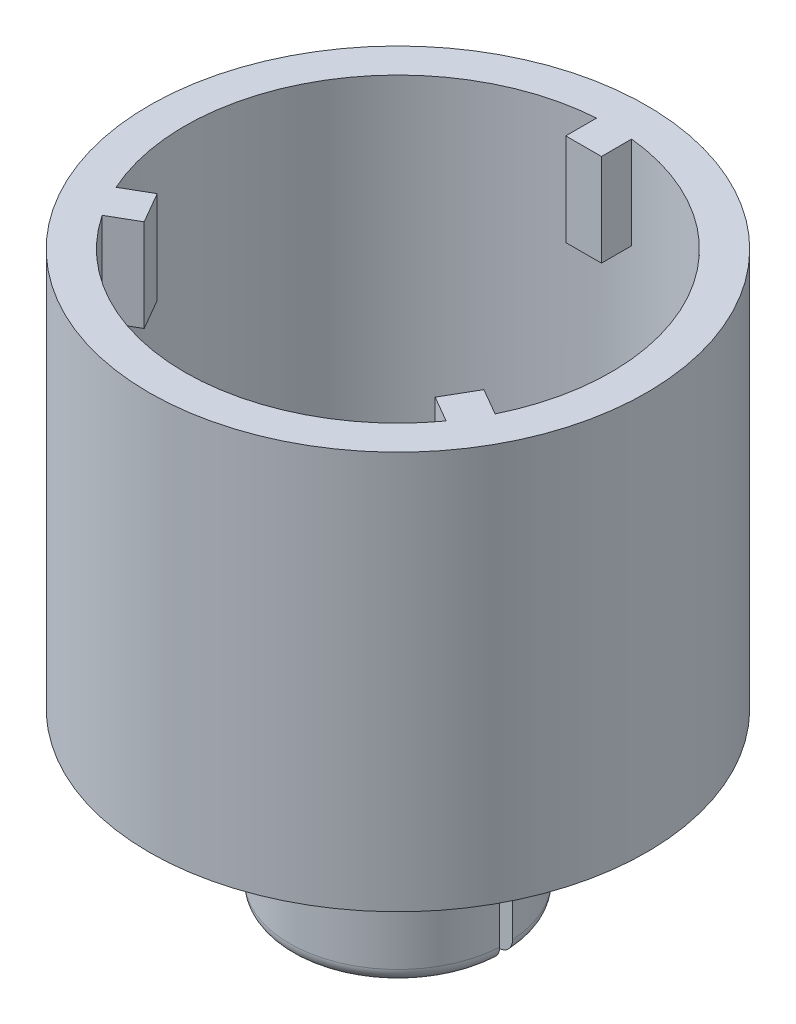
SolidWorks part; units mm, degrees
ref_plane "Front Plane" through (0, 0, 0) normal (0, 0, 1) x (1, 0, 0)
ref_plane "Top Plane" through (0, 0, 0) normal (0, 1, 0) x (1, 0, 0)
ref_plane "Right Plane" through (0, 0, 0) normal (1, 0, 0) x (0, 0, -1)
sketch "Sketch1" plane through (0, 0, 0) normal (0, 1, 0) x (1, 0, 0)
  circle A0 centre (0, 0) radius 35
  dimension "D1" = 70
extrude "Boss-Extrude1" add sketch "Sketch1" along normal blind 56
sketch "Sketch2" plane through (0, 56, 0) normal (0, 1, 0) x (1, 0, 0)
  circle A0 centre (0, 0) radius 30
  dimension "D1" = 60
extrude "Cut-Extrude1" cut sketch "Sketch2" against normal blind 46.9
sketch "Sketch3" plane through (0, 0, 0) normal (0, -1, 0) x (1, 0, 0)
  circle A0 centre (0, 0) radius 19.5
  dimension "D1" = 39
extrude "Boss-Extrude2" add sketch "Sketch3" along normal blind 7
sketch "Sketch4" plane through (0, -7, 0) normal (0, -1, 0) x (1, 0, 0)
  circle A0 centre (0, 0) radius 15.25
  dimension "D1" = 30.5
extrude "Boss-Extrude3" add sketch "Sketch4" along normal blind 16
fillet "Fillet1" radius 5 1 edges at (0, 0, -19.5)
sketch "Sketch5" plane through (0, 56, 0) normal (0, 1, 0) x (1, 0, 0)
  line L0 (-1.9905, 29.9339) -> (-1.9905, 25.6053)
  line L1 (-1.9905, 25.6053) -> (3.0302, 25.6053)
  line L2 (3.0302, 25.6053) -> (3.0302, 29.8466)
  line L3 (26.9188, -13.2431) -> (23.1701, -11.0788)
  line L4 (23.1701, -11.0788) -> (20.6597, -15.4269)
  line L5 (20.6597, -15.4269) -> (24.3328, -17.5475)
  line L6 (-24.9282, -16.6908) -> (-21.1796, -14.5265)
  line L7 (-21.1796, -14.5265) -> (-23.69, -10.1784)
  line L8 (-23.69, -10.1784) -> (-27.363, -12.299)
  circle A0 centre (0, 0) radius 30 construction
  arc A1 (24.3328, -17.5475) -> (26.9188, -13.2431) centre (0, 0) ccw
  circle A2 centre (0, 0) radius 30
  arc A3 (3.0302, 29.8466) -> (-1.9905, 29.9339) centre (0, 0) ccw
  arc A4 (-27.363, -12.299) -> (-24.9282, -16.6908) centre (0, 0) ccw
  point P19 (0, 0)
  dimension "D1" = 0
  dimension "D2" = 3
extrude "Boss-Extrude4" add sketch "Sketch5" against normal blind 13
sketch "Sketch7" plane through (0, -23, 0) normal (0, -1, 0) x (1, 0, 0)
  line L1 (33.0968, 0.9034) -> (-33.0968, 0.9034)
  line L2 (33.0968, 0.9034) -> (33.0968, -0.9034)
  line L3 (33.0968, -0.9034) -> (-33.0968, -0.9034)
  line L4 (-33.0968, 0.9034) -> (-33.0968, -0.9034)
  line L5 (33.0968, 0.9034) -> (-33.0968, -0.9034) construction
  line L6 (33.0968, -0.9034) -> (-33.0968, 0.9034) construction
  point P0 (0, 0)
extrude "Cut-Extrude2" cut sketch "Sketch7" against normal up to surface (16 mm away) up to face at (0, -7, -15.25)
fillet "Fillet2" radius 2 2 edges at (0, -23, 15.25) (0, -23, -15.25)
